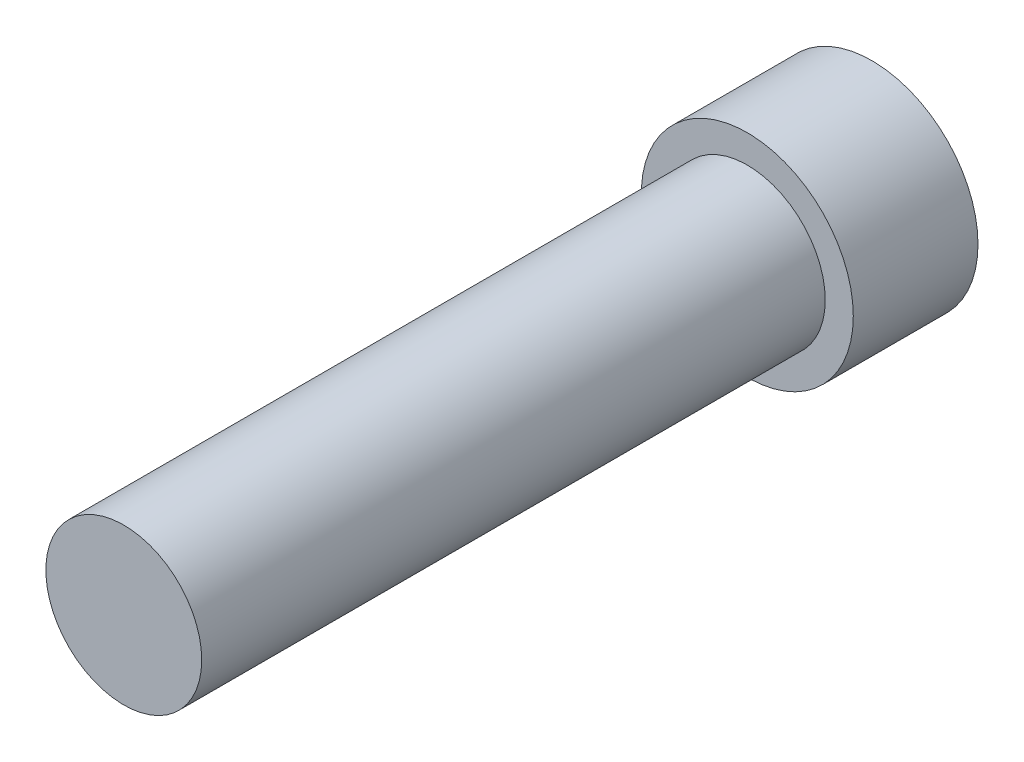
SolidWorks part; units mm, degrees
ref_plane "Front Plane" through (0, 0, 0) normal (0, 0, 1) x (1, 0, 0)
ref_plane "Top Plane" through (0, 0, 0) normal (0, 1, 0) x (1, 0, 0)
ref_plane "Right Plane" through (0, 0, 0) normal (1, 0, 0) x (0, 0, -1)
sketch "Sketch1" plane through (0, 0, 0) normal (0, 0, 1) x (1, 0, 0)
  circle A0 centre (0, 0) radius 1.25
  circle A1 centre (0, 0) radius 1.7
  dimension "D1" = 2.5
  dimension "D2" = 3.4
extrude "Boss-Extrude1" add sketch "Sketch1" along normal blind 12 contours A0 region at (0, 0, 0)
extrude "Boss-Extrude2" add sketch "Sketch1<3>" along normal blind 2
sketch "Sketch1<3>" plane through (0, 0, 0) normal (0, 0, 1) x (1, 0, 0) same geometry as "Sketch1"
sketch "Sketch3" plane through (0, 0, 0) normal (0, 0, -1) x (-1, 0, 0)
  line L1 (0.9881, -0.5975) -> (1.0115, 0.557)
  line L2 (1.0115, 0.557) -> (0.0234, 1.1545)
  line L3 (0.0234, 1.1545) -> (-0.9881, 0.5975)
  line L4 (-0.9881, 0.5975) -> (-1.0115, -0.557)
  line L5 (-1.0115, -0.557) -> (-0.0234, -1.1545)
  line L6 (-0.0234, -1.1545) -> (0.9881, -0.5975)
  circle A0 centre (0, 0) radius 1 construction
extrude "Cut-Extrude1" cut sketch "Sketch3" against normal blind 2
